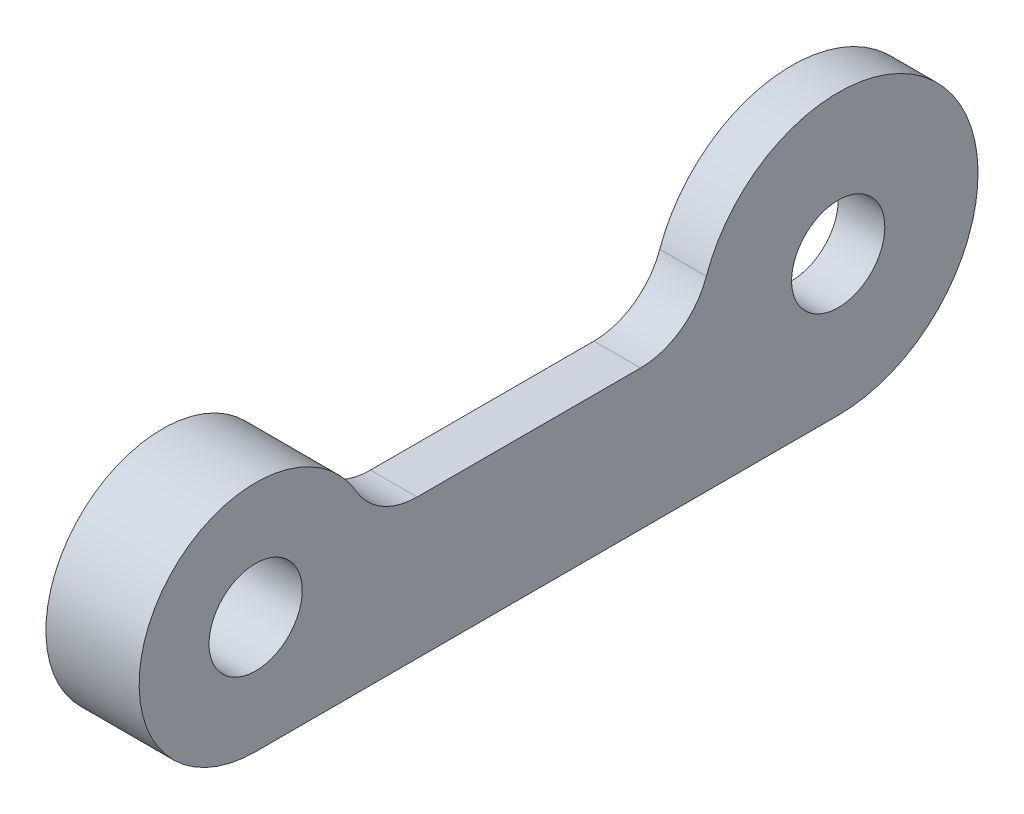
SolidWorks part; units mm, degrees
ref_plane "前视基准面" through (0, 0, 0) normal (0, 0, 1) x (1, 0, 0)
ref_plane "上视基准面" through (0, 0, 0) normal (0, 1, 0) x (1, 0, 0)
ref_plane "右视基准面" through (0, 0, 0) normal (1, 0, 0) x (0, 0, -1)
other "Configuration Table"
sketch "草图1" plane through (0, 0, 0) normal (1, 0, 0) x (0, 0, -1)
  line L1 (0, 0) -> (25, 0)
  line L2 (0, 0) -> (0, -6)
  line L3 (0, -6) -> (25, -6)
  line L4 (25, 0) -> (25, -6)
  circle A0 centre (0, -1) radius 5
  circle A1 centre (25, 0) radius 6
  circle A2 centre (0, -1) radius 2
  circle A3 centre (25, 0) radius 2
  dimension "D1" = 10
  dimension "D2" = 12
  dimension "D4" = 4
  dimension "D3" = 6
  dimension "D5" = 25
extrude "凸台-拉伸1" add sketch "草图1" along normal blind 2 contours A0 | L1 L4 L3 L2 | A1
extrude "凸台-拉伸3" add sketch "草图1<5>" against normal blind 2 contours A0
sketch "草图1<5>" plane through (0, 0, 0) normal (1, 0, 0) x (0, 0, -1) same geometry as "草图1"
extrude "切除-拉伸2" cut sketch "草图1<4>" along normal through all both and the other way through all contours L2 A2 | L2 A2 | L4 A3 L1 | L1 A3 L4 region at (0, -0.7694, 0.5991) region at (0, -1.3427, -0.8902) region at (0, 0.2829, -25.2829) region at (0, -0.8488, -24.1512)
sketch "草图1<4>" plane through (0, 0, 0) normal (1, 0, 0) x (0, 0, -1) same geometry as "草图1"
fillet "圆角1" radius 3 2 edges at (1, 0, -19) (1, 0, -4.899)
